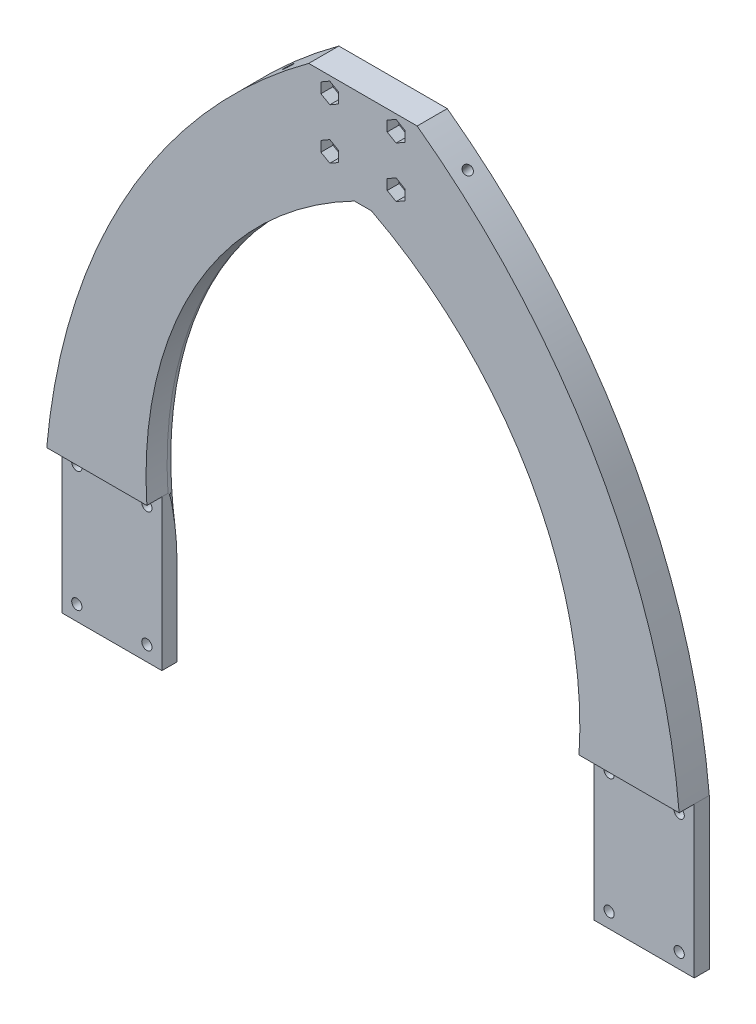
SolidWorks part; units mm, degrees
ref_plane "Ebene vorne" through (0, 0, 0) normal (0, 0, 1) x (1, 0, 0)
ref_plane "Ebene oben" through (0, 0, 0) normal (0, 1, 0) x (1, 0, 0)
ref_plane "Ebene rechts" through (0, 0, 0) normal (1, 0, 0) x (0, 0, -1)
sketch "Skizze1" plane through (0, 0, 0) normal (0, 1, 0) x (1, 0, 0)
  line L1 (-105, -210) -> (105, -210)
  line L2 (-105, -210) -> (-105, 210)
  line L3 (-105, 210) -> (105, 210)
  line L4 (105, -210) -> (105, 210)
  line L5 (-105, -210) -> (105, 210) construction
  line L6 (-105, 210) -> (105, -210) construction
  point P0 (0, 0)
  dimension "D1" = 210
  dimension "D2" = 420
extrude "Aufsatz-Linear austragen1" add sketch "Skizze1" along normal blind 10
ref_plane "Ebene1" through (0, -97.5366, 81.8429) normal (0, -0.766, 0.6428) x (1, 0, 0)
sketch "Skizze2" plane through (0, -97.5366, 81.8429) normal (0, -0.766, 0.6428) x (1, 0, 0)
  line L1 (-105, 167.2972) -> (105, 167.2972) construction
  circle A0 centre (0, 147.2972) radius 5
  dimension "D1" = 10
  dimension "D2" = 20
extrude "Schnitt-Linear austragen1" [suppressed] cut sketch "Skizze2" against normal blind 30 and the other way blind 10
sketch "Skizze3" [suppressed] plane through (0, -67.9923, 57.0523) normal (0, -0.766, 0.6428) x (1, 0, 0)
  circle A0 centre (0, 101.3345) radius 5
  dimension "D1" = 10
extrude "Aufsatz-Linear austragen2" [suppressed] add sketch "Skizze3" along normal blind 0.1
sketch "Skizze4" plane through (0, -97.5366, 81.8429) normal (0, -0.766, 0.6428) x (1, 0, 0)
  line L0 (0, 167.2972) -> (0, 159.9002) construction
  line L1 (-105, 167.2972) -> (105, 167.2972) construction
  line L2 (-25, 167.2972) -> (-25, 202.2972)
  line L3 (-25, 202.2972) -> (25, 202.2972)
  line L4 (-25, 167.2972) -> (25, 167.2972)
  line L5 (25, 167.2972) -> (25, 202.2972)
  point P10 (0, 202.2972)
  dimension "D1" = 50
  dimension "D2" = 35
extrude "Aufsatz-Linear austragen3" [suppressed] add sketch "Skizze4" against normal blind 10 separate body
sketch "Skizze5" plane through (0, 10, 0) normal (0, 1, 0) x (1, 0, 0)
  line L0 (0, 0) -> (0, -210) construction
  line L1 (-105, -210) -> (105, -210) construction
  line L2 (105, -210) -> (18, -210)
  line L3 (-18, -210) -> (-105, -56)
  line L4 (-105, 210) -> (-105, -210) construction
  line L5 (-105, -56) -> (-105, -210)
  line L6 (-105, -210) -> (-18, -210)
  line L7 (105, -56) -> (105, -210)
  line L8 (18, -210) -> (105, -56)
  line L9 (-105, 210) -> (-105, 125)
  line L10 (-105, 125) -> (105, 125)
  line L11 (105, -210) -> (105, 210) construction
  line L12 (105, 125) -> (105, 210)
  line L13 (105, 210) -> (-105, 210)
  line L14 (71.7468, -56) -> (-71.7468, -56)
  line L15 (-71.7468, -56) -> (-2.8247, -178)
  line L16 (71.7468, -56) -> (2.8247, -178)
  line L17 (-2.8247, -178) -> (2.8247, -178)
  line L18 (2.8247, -178) -> (0, -183) construction
  line L19 (-2.8247, -178) -> (0, -183) construction
  point P27 (0, -56)
  dimension "D1" = 36
  dimension "D2" = 154
  dimension "D3" = 85
  dimension "D4" = 32
  dimension "D5" = 27
extrude "Schnitt-Linear austragen2" cut sketch "Skizze5" against normal blind 10
sketch "Skizze6" plane through (0, 10, 0) normal (0, 1, 0) x (1, 0, 0)
  line L0 (0, -210) -> (0, -178) construction
  line L1 (-18, -210) -> (18, -210) construction
  line L2 (-2.8247, -178) -> (2.8247, -178) construction
  line L3 (0, -196.59) -> (-21.075, -196.59) construction
  circle A0 centre (-11, -205) radius 1.7
  circle A1 centre (-11, -188.18) radius 1.7
  circle A2 centre (11, -205) radius 1.7
  circle A3 centre (11, -188.18) radius 1.7
  dimension "D1" = 3.4
  dimension "D2" = 11
  dimension "D3" = 5
  dimension "D4" = 13.41
extrude "Schnitt-Linear austragen3" cut sketch "Skizze6" against normal through all
sketch "Skizze7" plane through (0, 0, 0) normal (0, -1, 0) x (1, 0, 0)
  line L0 (-11, 205) -> (-11, 210) construction
  line L1 (-18, 210) -> (18, 210) construction
  line L2 (-11, 205) -> (-5.1092, 205) construction
  line L3 (-11, 208.4064) -> (-8.05, 206.7032)
  line L4 (-8.05, 206.7032) -> (-8.05, 203.2968)
  line L5 (-11, 201.5936) -> (-8.05, 203.2968)
  line L6 (-11, 201.5936) -> (-13.95, 203.2968)
  line L7 (-13.95, 206.7032) -> (-13.95, 203.2968)
  line L8 (-11, 208.4064) -> (-13.95, 206.7032)
  line L9 (0, 210) -> (0, 121.6034) construction
  line L10 (11, 205) -> (11, 188.18) construction
  line L11 (11, 196.59) -> (0, 196.59) construction
  line L12 (11, 208.4064) -> (8.05, 206.7032)
  line L13 (11, 201.5936) -> (8.05, 203.2968)
  line L14 (8.05, 206.7032) -> (8.05, 203.2968)
  line L15 (11, 201.5936) -> (13.95, 203.2968)
  line L16 (13.95, 206.7032) -> (13.95, 203.2968)
  line L17 (11, 208.4064) -> (13.95, 206.7032)
  line L18 (-8.05, 186.4768) -> (-8.05, 189.8832)
  line L19 (-11, 191.5864) -> (-13.95, 189.8832)
  line L20 (-11, 191.5864) -> (-8.05, 189.8832)
  line L21 (-13.95, 186.4768) -> (-13.95, 189.8832)
  line L22 (-11, 184.7736) -> (-13.95, 186.4768)
  line L23 (-11, 184.7736) -> (-8.05, 186.4768)
  line L24 (8.05, 186.4768) -> (8.05, 189.8832)
  line L25 (11, 191.5864) -> (8.05, 189.8832)
  line L26 (11, 191.5864) -> (13.95, 189.8832)
  line L27 (13.95, 186.4768) -> (13.95, 189.8832)
  line L28 (11, 184.7736) -> (13.95, 186.4768)
  line L29 (11, 184.7736) -> (8.05, 186.4768)
  point P10 (-8.05, 205)
  dimension "D1" = 120
  dimension "D2" = 5.9
extrude "Schnitt-Linear austragen4" cut sketch "Skizze7" against normal blind 4
sketch "Skizze8" plane through (0, 10, 0) normal (0, 1, 0) x (1, 0, 0)
  line L0 (105, 115.41) -> (78.872, 115.41) construction
  line L1 (105, -56) -> (105, 125) construction
  line L2 (-105, 125) -> (105, 125) construction
  dimension "D1" = 9.59
ref_plane "Ebene2" through (0, 62.6966, -52.6087) normal (0, 0.766, -0.6428) x (-1, 0, 0)
sketch "Skizze9" plane through (0, 62.6966, -52.6087) normal (0, 0.766, -0.6428) x (-1, 0, 0)
  line L0 (-105, -81.9813) -> (-78.872, -81.9813) construction
  line L1 (-105, 49.3264) -> (-105, -89.3277) construction
  line L2 (0, -45.2589) -> (0, -16.2619) construction
  circle A0 centre (-100, -81.9813) radius 1.7
  circle A1 centre (100, -81.9813) radius 1.7
  circle A2 centre (-30, -81.9813) radius 1.7
  circle A3 centre (30, -81.9813) radius 1.7
  dimension "D1" = 3.4
  dimension "D2" = 5
  dimension "D3" = 30
extrude "Schnitt-Linear austragen5" [suppressed] cut sketch "Skizze9" against normal through all and the other way through all
ref_plane "Ebene3" through (0, 55.0361, -46.1808) normal (0, 0.766, -0.6428) x (-1, 0, 0)
sketch "Skizze10" [suppressed] plane through (0, 55.0361, -46.1808) normal (0, 0.766, -0.6428) x (-1, 0, 0)
  line L0 (-95, -81.9813) -> (-100, -81.9813) construction
  line L1 (-95, -81.9813) -> (-95, -30.0694) construction
  line L2 (-95, -78.7482) -> (-97.8, -80.3647)
  line L3 (-97.8, -80.3647) -> (-97.8, -83.5979)
  line L4 (-95, -85.2145) -> (-97.8, -83.5979)
  line L5 (-95, -85.2145) -> (-92.2, -83.5979)
  line L6 (-92.2, -80.3647) -> (-92.2, -83.5979)
  line L7 (-95, -78.7482) -> (-92.2, -80.3647)
  line L8 (0, 0) -> (0, -45.6283) construction
  line L9 (-30, -81.9813) -> (-95, -81.9813) construction
  line L10 (-62.5, -81.9813) -> (-62.5, -23.1343) construction
  line L11 (-32.8, -80.3647) -> (-32.8, -83.5979)
  line L12 (-30, -85.2145) -> (-32.8, -83.5979)
  line L13 (-30, -85.2145) -> (-27.2, -83.5979)
  line L14 (-27.2, -80.3647) -> (-27.2, -83.5979)
  line L15 (-30, -78.7482) -> (-27.2, -80.3647)
  line L16 (-30, -78.7482) -> (-32.8, -80.3647)
  line L17 (95, -78.7482) -> (92.2, -80.3647)
  line L18 (92.2, -80.3647) -> (92.2, -83.5979)
  line L19 (95, -85.2145) -> (92.2, -83.5979)
  line L20 (95, -85.2145) -> (97.8, -83.5979)
  line L21 (97.8, -80.3647) -> (97.8, -83.5979)
  line L22 (95, -78.7482) -> (97.8, -80.3647)
  line L23 (30, -78.7482) -> (32.8, -80.3647)
  line L24 (30, -78.7482) -> (27.2, -80.3647)
  line L25 (27.2, -80.3647) -> (27.2, -83.5979)
  line L26 (30, -85.2145) -> (27.2, -83.5979)
  line L27 (30, -85.2145) -> (32.8, -83.5979)
  line L28 (32.8, -80.3647) -> (32.8, -83.5979)
  point P9 (-97.8, -81.9813)
  point P31 (97.8, -81.9813)
  dimension "D1" = 120
  dimension "D2" = 5.6
extrude "Schnitt-Linear austragen6" [suppressed] cut sketch "Skizze10" against normal blind 10 and the other way blind 5
sketch "Skizze13" plane through (0, 10, 0) normal (0, 1, 0) x (1, 0, 0)
  line L0 (71.7468, -56) -> (105, -56) construction
  line L1 (71.7468, -56) -> (96.9548, -70.2409) construction
  line L2 (105, -56) -> (18, -210) construction
  line L3 (0, 0) -> (0, -38.1435) construction
  line L4 (2.8247, -178) -> (71.7468, -56) construction
  line L5 (84.3508, -63.1205) -> (108.762, -19.9098) construction
  line L6 (105, -56) -> (105, 125) construction
  line L7 (88.3734, -56) -> (88.3734, -1) construction
  line L8 (99, -58.9512) -> (105.7595, -46.9862) construction
  line L9 (87.7845, -86.4734) -> (62.5765, -72.2325) construction
  line L10 (77.1638, -80.4734) -> (91.1741, -80.4734) construction
  circle A0 centre (99, -58.9512) radius 1.7
  circle A1 centre (76.9708, -58.9512) radius 1.7
  circle A2 centre (86.8414, -80.4734) radius 1.7
  circle A3 centre (-86.8414, -80.4734) radius 1.7
  circle A4 centre (-99, -58.9512) radius 1.7
  circle A5 centre (-76.9708, -58.9512) radius 1.7
  dimension "D1" = 6
  dimension "D5" = 35
  dimension "D3" = 3.4
  dimension "D6" = 3.4
  dimension "D2" = 6
  dimension "D4" = 6
extrude "Schnitt-Linear austragen7" [suppressed] cut sketch "Skizze13" against normal through all
sketch "Skizze14" plane through (103.579, 0, 58.5154) normal (0.8707, 0, 0.4919) x (0.4919, 0, -0.8707)
  line L0 (-32.111, 5) -> (-32.111, 10)
  line L5 (2.889, 0) -> (2.889, 10) construction
  line L6 (-32.111, 5) -> (2.889, 5)
  line L7 (2.889, 10) -> (-173.9866, 10) construction
  line L8 (-32.111, 10) -> (2.889, 10)
  line L9 (2.889, 10) -> (2.889, 5)
  dimension "D1" = 35
extrude "Schnitt-Linear austragen8" [suppressed] cut sketch "Skizze14" against normal up to surface (28.9525 mm away) up to face at (37.2857, 5, 117)
mirror "Spiegeln1" [suppressed] about plane through (0, 0, 0) normal (1, 0, 0)
sketch "Skizze15" [suppressed] plane through (95, 0, 0) normal (1, 0, 0) x (0, 0, -1)
  line L0 (4, 10) -> (4, 0)
  line L1 (4, 0) -> (65, 0)
  line L2 (65, 0) -> (65, 10)
  line L3 (65, 10) -> (4, 10)
extrude "Schnitt-Linear austragen9" [suppressed] cut sketch "Skizze15" against normal through all
sketch "Skizze16" plane through (0, 0, 0) normal (0, -1, 0) x (1, 0, 0)
  line L0 (0, 210) -> (0, 178) construction
  line L1 (-18, 210) -> (18, 210) construction
  line L2 (-2.8247, 178) -> (2.8247, 178) construction
  line L3 (11, 196.59) -> (0, 196.59) construction
  line L4 (11, 205) -> (11, 188.18) construction
  line L6 (-17.5, 193.09) -> (17.5, 193.09)
  line L7 (-17.5, 193.09) -> (-17.5, 200.09)
  line L8 (-17.5, 200.09) -> (17.5, 200.09)
  line L9 (17.5, 193.09) -> (17.5, 200.09)
  line L10 (-17.5, 193.09) -> (17.5, 200.09) construction
  line L11 (-17.5, 200.09) -> (17.5, 193.09) construction
  dimension "D1" = 7
  dimension "D2" = 35
extrude "Schnitt-Linear austragen10" [suppressed] cut sketch "Skizze16" against normal blind 5
sketch "Skizze17" [suppressed] plane through (17.5, 0, 0) normal (-1, 0, 0) x (0, 0, 1)
  line L0 (196.59, 0) -> (196.59, 11.1261) construction
  line L1 (193.09, 0) -> (200.09, 0) construction
  line L2 (193.09, 5) -> (196.59, 8.5)
  line L3 (196.59, 8.5) -> (200.09, 5)
  line L4 (200.09, 5) -> (193.09, 5)
  dimension "D1" = 90
extrude "Schnitt-Linear austragen11" [suppressed] cut sketch "Skizze17" along normal up to surface (35 mm away)
sketch "Skizze18" [suppressed] plane through (0, 10, 0) normal (0, 1, 0) x (1, 0, 0)
  line L0 (0, -210) -> (0, 0) construction
  line L1 (-18, -210) -> (18, -210) construction
  line L2 (62.5765, -72.2325) -> (35.4483, -67.5372)
  line L3 (15.3378, -155.8503) -> (-22.1774, -134.6566)
  line L4 (2.8247, -178) -> (62.5765, -72.2325) construction
  line L5 (-15.3378, -155.8503) -> (22.1774, -134.6566)
  line L6 (58.6594, -79.166) -> (40.7308, -76.063)
  line L7 (0, -147.1854) -> (19.5429, -147.1854) construction
  line L8 (0, -95.4) -> (31.4297, -95.4) construction
  line L9 (11.6488, -162.3803) -> (0, -155.7995)
  line L10 (-71.7468, -56) -> (-2.8247, -178) construction
  line L11 (0, -95.4) -> (-37.5153, -116.5937) construction
  line L12 (-37.5153, -116.5937) -> (-39.2566, -117.5774) construction
  line L13 (-11.6488, -162.3803) -> (0, -155.7995)
  line L14 (-58.6594, -79.166) -> (-40.7308, -76.063)
  line L15 (-62.5765, -72.2325) -> (-35.4483, -67.5372)
  circle A0 centre (0, -95.4) radius 33.5
  arc A1 (7.4594, -151.3994) -> (7.4594, -142.9713) centre (9.84, -147.1854) cw
  arc A2 (-7.4594, -151.3994) -> (-7.4594, -142.9713) centre (-9.84, -147.1854) ccw
  circle A3 centre (0, -95.4) radius 45.0879
  point P17 (0, -147.1854)
  point P36 (5, -147.1854)
  point P40 (-5, -147.1854)
  line M16 (62.5765, -72.2325) -> (2.8247, -178)
  line M18 (-2.8247, -178) -> (-71.7468, -56)
  dimension "D2" = 67
  dimension "D5" = 2
  dimension "D4" = 10
  dimension "D1" = 114.6
  dimension "D3" = 7.5
  dimension "D6" = 7.5
extrude "Aufsatz-Linear austragen4" [suppressed] add sketch "Skizze18" against normal blind 10 contours A3 L15 L14 M18 | A3 A0 M16 M18 | A3 L6 L2 M16 | A2 L5 L3 | A3 L3 L5 | L3 A1 L5 | L13 L9 L3 L5 M18 M16
sketch "Skizze19" [suppressed] plane through (0, 0, 0) normal (0, -1, 0) x (1, 0, 0)
  circle A0 centre (0, 35.4) radius 31.5
  circle A1 centre (0, 35.4) radius 33.5
  circle A2 centre (0, 35.4) radius 33.5 construction
  dimension "D1" = 63
extrude "Aufsatz-Linear austragen5" [suppressed] add sketch "Skizze19" against normal blind 1
sketch "Skizze20" plane through (0, 10, 0) normal (0, 1, 0) x (1, 0, 0)
  line L0 (105, 119.52) -> (55.4083, 119.52) construction
  line L1 (105, -56) -> (105, 125) construction
  line L2 (-105, 125) -> (105, 125) construction
  line L3 (0, 125) -> (0, 96.9732) construction
  line L4 (105, 43.82) -> (35.5869, 43.82) construction
  circle A0 centre (96, 119.52) radius 1.7
  circle A1 centre (54, 119.52) radius 1.7
  circle A2 centre (-54, 119.52) radius 1.7
  circle A3 centre (-96, 119.52) radius 1.7
  circle A4 centre (92.5, 43.82) radius 1.7
  circle A5 centre (57.5, 43.82) radius 1.7
  circle A6 centre (-92.5, 43.82) radius 1.7
  circle A7 centre (-57.5, 43.82) radius 1.7
  dimension "D1" = 3.4
  dimension "D2" = 5.48
  dimension "D3" = 9
  dimension "D4" = 42
  dimension "D5" = 75.7
  dimension "D6" = 12.5
  dimension "D7" = 35
extrude "Schnitt-Linear austragen12" cut sketch "Skizze20" against normal through all
sketch "Skizze21" plane through (0, 10, 0) normal (0, 1, 0) x (1, 0, 0)
  line L0 (-71.7468, -56) -> (-71.7468, 19)
  line L1 (-71.7468, 19) -> (71.7468, 19)
  line L2 (71.7468, 19) -> (71.7468, -56)
  line L3 (71.7468, -56) -> (-71.7468, -56) construction
  line L4 (-71.7468, -56) -> (71.7468, -56)
  dimension "D1" = 75
extrude "Schnitt-Linear austragen13" cut sketch "Skizze21" against normal through all
sketch "Skizze22" plane through (0, 10, 0) normal (0, 1, 0) x (1, 0, 0)
  line L0 (-71.7468, -56) -> (-2.8247, -178)
  arc A0 (-71.7468, -56) -> (-2.8247, -178) centre (55.7113, -64.4627) ccw
  line M19 (-2.8247, -178) -> (-71.7468, -56)
extrude "Schnitt-Linear austragen14" cut sketch "Skizze22" against normal through all contours M19 region at (-44.6278, 10, 121.1478)
sketch "Skizze23" plane through (0, 10, 0) normal (0, 1, 0) x (1, 0, 0)
  line L0 (-18, -210) -> (-105, -56) construction
  line L1 (-105, -56) -> (-18, -210)
  arc A0 (-18, -210) -> (-105, -56) centre (108.9155, -36.7263) cw
  arc A2 (-71.7468, -56) -> (-2.8247, -178) centre (55.7113, -64.4627) ccw construction
  dimension "D1" = 60
extrude "Aufsatz-Linear austragen6" add sketch "Skizze23" against normal blind 10
mirror "Spiegeln2" about plane through (0, 0, 0) normal (1, 0, 0) of "Aufsatz-Linear austragen6", "Schnitt-Linear austragen14"
sketch "Skizze25" plane through (0, 10, 0) normal (0, 1, 0) x (1, 0, 0)
  line L0 (-105, -56) -> (-71.7468, -56) construction
  line L1 (-105, -6) -> (-105, -56) construction
  line L2 (-105, -6) -> (-71.7468, -6) construction
  line L3 (-71.7468, 19) -> (-71.7468, -56) construction
  line L4 (-88.3734, -6) -> (-88.3734, -56) construction
  line L5 (-105, -31) -> (-71.7468, -31) construction
  line L6 (-105, 125) -> (-105, -56) construction
  circle A0 centre (-100, -11) radius 1.7
  circle A1 centre (-76.7468, -11) radius 1.7
  circle A2 centre (-76.7468, -51) radius 1.7
  circle A3 centre (-100, -51) radius 1.7
  dimension "D2" = 3.4
  dimension "D1" = 50
  dimension "D3" = 5
  dimension "D4" = 5
extrude "Schnitt-Linear austragen15" cut sketch "Skizze25" against normal through all
sketch "Skizze26" plane through (-105, 0, 0) normal (-1, 0, 0) x (0, 0, 1)
  line L0 (56, 5) -> (56, 0)
  line L1 (56, 0) -> (56, 10) construction
  line L2 (56, 5) -> (6, 5)
  line L3 (6, 5) -> (6, 10)
  line L4 (-125, 0) -> (56, 0) construction
  line L5 (5.0128, 19.5087) -> (6, 10)
  line L6 (5.0128, 19.5087) -> (-137.7077, 19.5087)
  line L7 (-137.7077, 19.5087) -> (-137.7077, -14.4017)
  line L8 (-137.7077, -14.4017) -> (4.1968, -14.4017)
  line L9 (4.1968, -14.4017) -> (56, 0)
  line L10 (-125, 10) -> (56, 10) construction
mirror "Spiegeln3" about plane through (0, 0, 0) normal (1, 0, 0) of "Schnitt-Linear austragen15"
extrude "Schnitt-Linear austragen16" cut sketch "Skizze26" against normal through all
fillet "Verrundung1" radius 3 3 edges at (55.5067, 10, 127.2937) (-55.5067, 10, 127.2937) (0, 10, 178)
sketch "Skizze27" plane through (0, 0, 0) normal (0, -1, 0) x (1, 0, 0)
  line L0 (18, 210) -> (40.9051, 190.6259) construction
  arc A0 (105, 56) -> (18, 210) centre (-108.9155, 36.7263) ccw construction
  dimension "D1" = 30
ref_plane "Ebene4" through (111.0524, 0, 131.2926) normal (0.6458, 0, 0.7635) x (0.7635, 0, -0.6458)
sketch "Skizze28" plane through (111.0524, 0, 131.2926) normal (0.6458, 0, 0.7635) x (0.7635, 0, -0.6458)
  line L0 (-106.8754, 0) -> (-106.8754, 10) construction
  line L1 (-121.8754, 0) -> (-91.8754, 0) construction
  line L2 (44.003, 10) -> (-121.8754, 10) construction
  circle A0 centre (-106.8754, 5) radius 1.5
  dimension "D1" = 3
extrude "Schnitt-Linear austragen17" cut sketch "Skizze28" against normal blind 8 and the other way blind 10
mirror "Spiegeln4" about plane through (0, 0, 0) normal (1, 0, 0) of "Schnitt-Linear austragen17"
move or copy body "Körper-Verschieben/Kopieren1" bodies to move or copy 127 copy no rotation origin (0, 5.338, 108) rotation axis (-1, 0, 0) rotation angle 90
